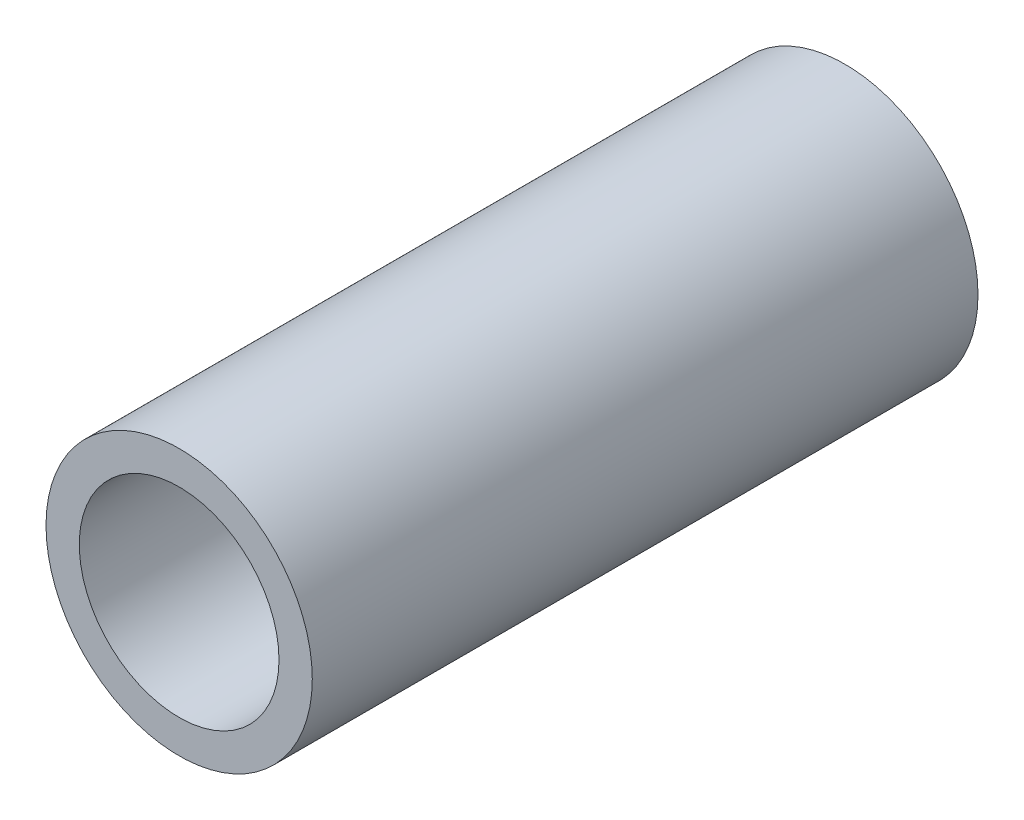
SolidWorks part; units mm, degrees
ref_plane "Plan de face" through (0, 0, 0) normal (0, 0, 1) x (1, 0, 0)
ref_plane "Plan de dessus" through (0, 0, 0) normal (0, 1, 0) x (1, 0, 0)
ref_plane "Plan de droite" through (0, 0, 0) normal (1, 0, 0) x (0, 0, -1)
sketch "Esquisse1" plane through (0, 0, 0) normal (0, 0, 1) x (1, 0, 0)
  circle A0 centre (0, 0) radius 4
  dimension "D1" = 8
extrude "Boss.-Extru.1" add sketch "Esquisse1" along normal blind 20
sketch "Esquisse2" plane through (0, 0, 20) normal (0, 0, 1) x (1, 0, 0)
  circle A0 centre (0, 0) radius 3
  dimension "D1" = 6
extrude "Enlèv. mat.-Extru.1" cut sketch "Esquisse2" against normal blind 5
